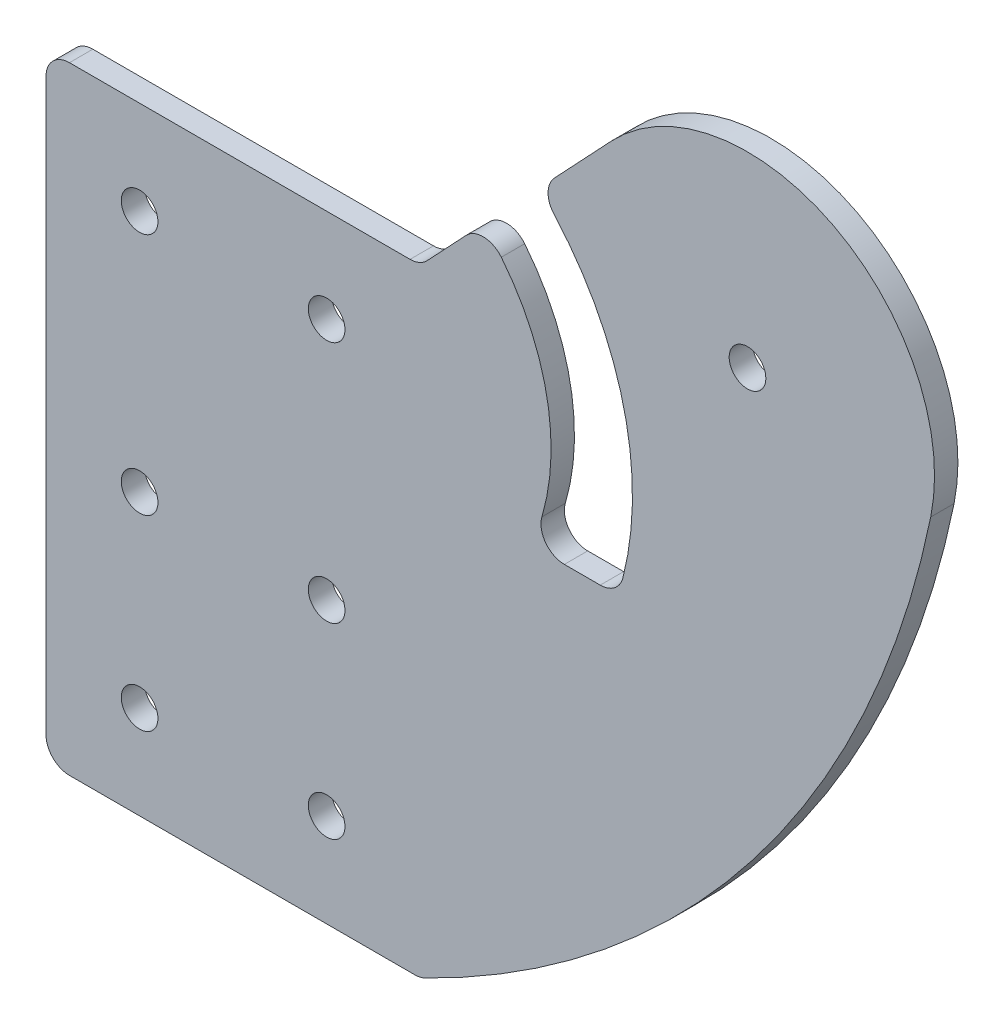
SolidWorks part; units mm, degrees
material "6061-T6 (SS)"
ref_plane "Front Plane" through (0, 0, 0) normal (0, 0, 1) x (1, 0, 0)
ref_plane "Top Plane" through (0, 0, 0) normal (0, 1, 0) x (1, 0, 0)
ref_plane "Right Plane" through (0, 0, 0) normal (1, 0, 0) x (0, 0, -1)
sketch "Sketch2" plane through (0, 0, 0) normal (0, 0, 1) x (1, 0, 0)
  line L0 (50.8, 83.82) -> (59.1187, 92.6561)
  line L1 (0, 0) -> (50.8, 0)
  line L2 (0, 0) -> (0, 83.82)
  line L3 (0, 83.82) -> (50.8, 83.82)
  line L11 (59.1187, 92.6561) -> (59.384, 92.938)
  line L12 (65.8081, 58.42) -> (77.6394, 58.42)
  line L14 (76.7561, 111.3908) -> (66.9585, 100.9837)
  circle A2 centre (95.25, 93.98) radius 2.4892
  arc A3 (50.8, 0) -> (120.1297, 88.8651) centre (-4.2686, 114.4397) ccw
  circle A4 centre (38.1, 71.12) radius 2.4892 construction
  circle A5 centre (13.208, 97.028) radius 4.7625 construction
  arc A8 (120.1297, 88.8651) -> (76.7561, 111.3908) centre (95.25, 93.98) ccw
  arc A9 (65.8081, 58.42) -> (59.384, 92.938) centre (38.1, 71.12) ccw
  arc A10 (77.6394, 58.42) -> (66.9585, 100.9837) centre (38.1, 71.12) ccw
  dimension "D3" = 50.8
  dimension "D5" = 95.25
  dimension "D4" = 4.9784
  dimension "D7" = 254
  dimension "D11" = 4.9784
  dimension "D8" = 60.96
  dimension "D9" = 83.058
  dimension "D16" = 9.525
  dimension "D1" = 50.8
  dimension "D2" = 83.82
  dimension "D6" = 93.98
  dimension "D10" = 25.4
  dimension "D12" = 38.1
  dimension "D13" = 12.7
  dimension "D14" = 25.908
  dimension "D15" = 24.892
extrude "Boss-Extrude1" add sketch "Sketch2" against normal blind 3.175
sketch "Sketch3" plane through (0, 0, 0) normal (0, 0, 1) x (1, 0, 0)
  line L0 (50.8, 83.82) -> (0, 83.82) construction
  line L1 (0, 83.82) -> (0, 0) construction
  circle A0 centre (12.7, 71.12) radius 2.4892
  circle A17 centre (38.1, 71.12) radius 2.4892
  circle A24 centre (12.7, 38.1) radius 2.4892
  circle A25 centre (12.7, 12.7) radius 2.4892
  circle A26 centre (12.7, -12.7) radius 2.4892
  circle A27 centre (12.7, -38.1) radius 2.4892
  circle A28 centre (12.7, -63.5) radius 2.4892
  circle A33 centre (38.1, 12.7) radius 2.4892
  circle A34 centre (38.1, -12.7) radius 2.4892
  circle A35 centre (38.1, -38.1) radius 2.4892
  circle A36 centre (38.1, -63.5) radius 2.4892
  circle A41 centre (38.1, 38.1) radius 2.4892
  dimension "D1" = 4.9784
  dimension "D6" = 4.9784
  dimension "D5" = 4.9784
  dimension "D2" = 12.7
  dimension "D3" = 12.7
  dimension "D7" = 12.7
  dimension "D8" = 33.02
  dimension "D4" = 1
  dimension "D9" = 5
  dimension "D10" = 2
extrude "Cut-Extrude1" cut sketch "Sketch3" against normal through all
fillet "Fillet1" radius 3.175 8 edges at (0, 0, -1.5875) (50.8, 83.82, -1.5875) (0, 83.82, -1.5875) (50.8, 0, -1.5875) (77.6394, 58.42, -1.5875) (65.8081, 58.42, -1.5875) (59.384, 92.938, -1.5875) (66.9585, 100.9837, -1.5875)
